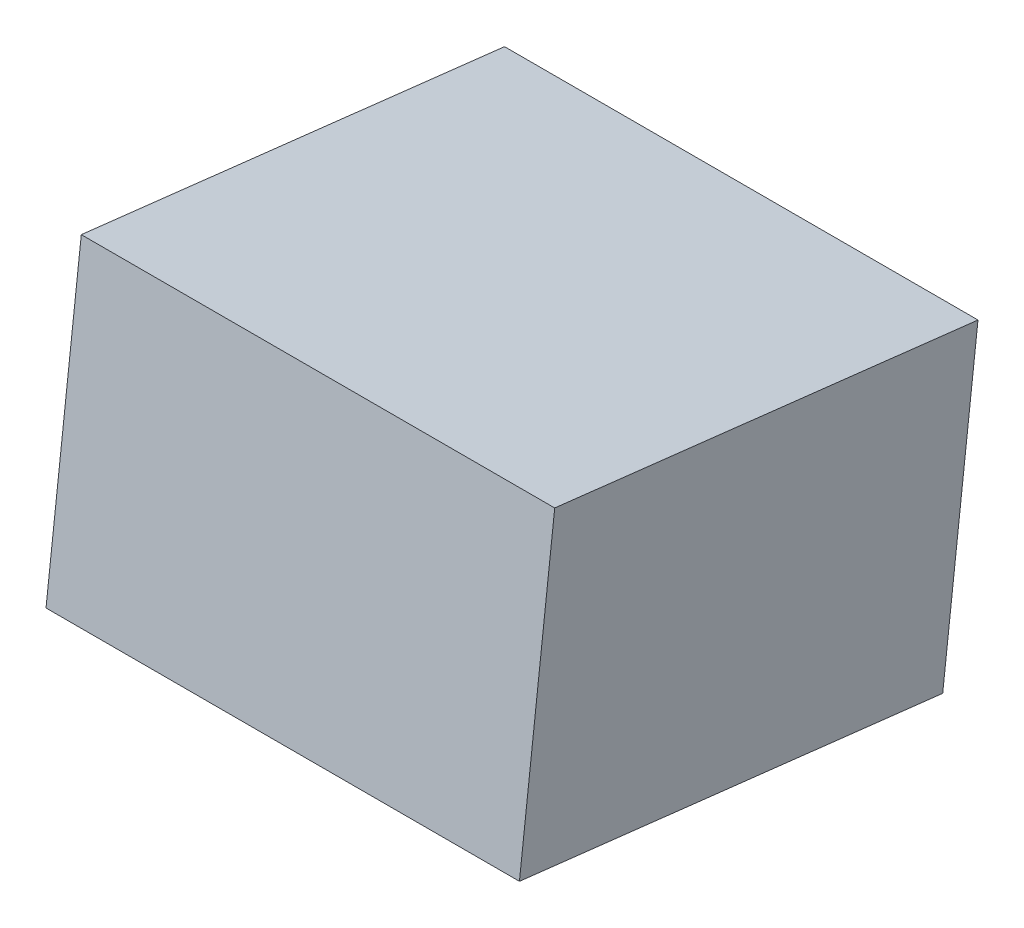
SolidWorks part; units mm, degrees
ref_plane "Front Plane" through (0, 0, 0) normal (0, 0, 1) x (1, 0, 0)
ref_plane "Top Plane" through (0, 0, 0) normal (0, 1, 0) x (1, 0, 0)
ref_plane "Right Plane" through (0, 0, 0) normal (1, 0, 0) x (0, 0, -1)
sketch "Sketch1" plane through (0, 358.8799, -41.4225) normal (0, 0.9934, -0.1147) x (1, 0, 0)
  line L1 (-235, 121.357) -> (-35, 121.357)
  line L2 (-235, 121.357) -> (-235, 301.357)
  line L3 (-235, 301.357) -> (-35, 301.357)
  line L4 (-35, 121.357) -> (-35, 301.357)
  line L5 (-235, 121.357) -> (-35, 301.357) construction
  line L6 (-235, 301.357) -> (-35, 121.357) construction
  point P0 (-135, 211.357)
  dimension "D1" = 180
  dimension "D2" = 200
extrude "Boss-Extrude1" add sketch "Sketch1" along normal blind 130
